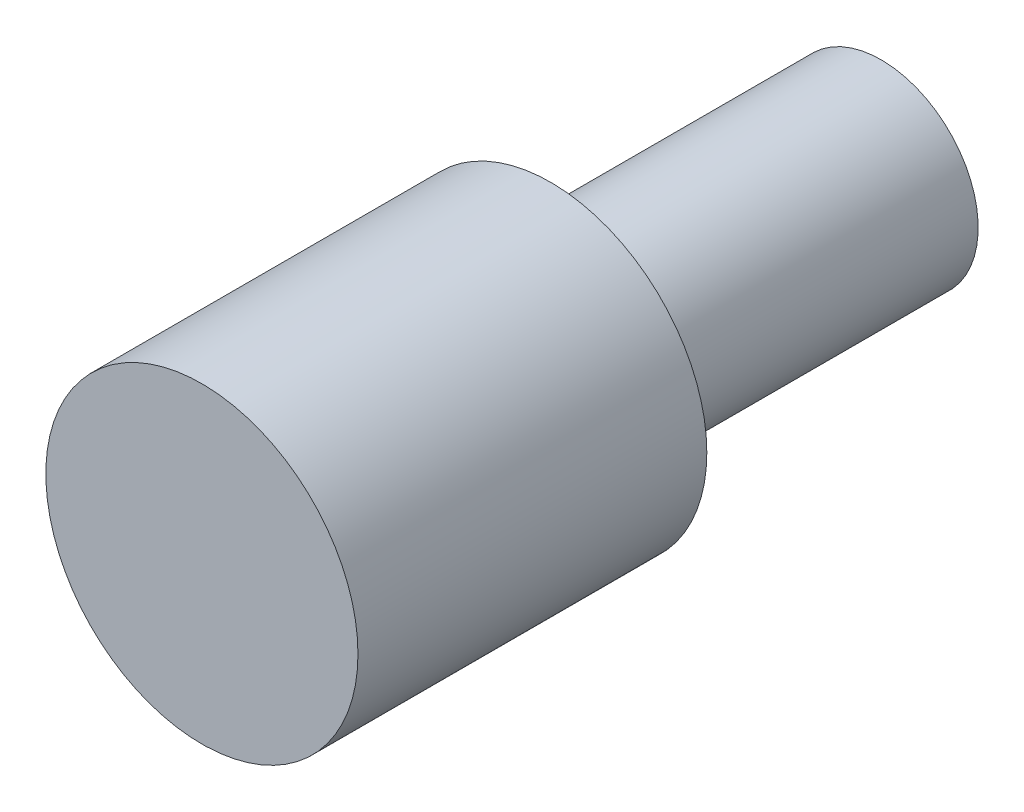
SolidWorks part; units mm, degrees
ref_plane "前视基准面" through (0, 0, 0) normal (0, 0, 1) x (1, 0, 0)
ref_plane "上视基准面" through (0, 0, 0) normal (0, 1, 0) x (1, 0, 0)
ref_plane "右视基准面" through (0, 0, 0) normal (1, 0, 0) x (0, 0, -1)
sketch "草图1" plane through (0, 0, 0) normal (0, 0, 1) x (1, 0, 0)
  circle A0 centre (0, 0) radius 7.65
  dimension "D1" = 15.3
extrude "凸台-拉伸1" add sketch "草图1" along normal blind 17.1
sketch "草图3" plane through (0, 0, 0) normal (0, 0, -1) x (-1, 0, 0)
  circle A0 centre (0, 0) radius 4.75
  dimension "D1" = 9.5
extrude "凸台-拉伸2" add sketch "草图3" along normal blind 16.2
